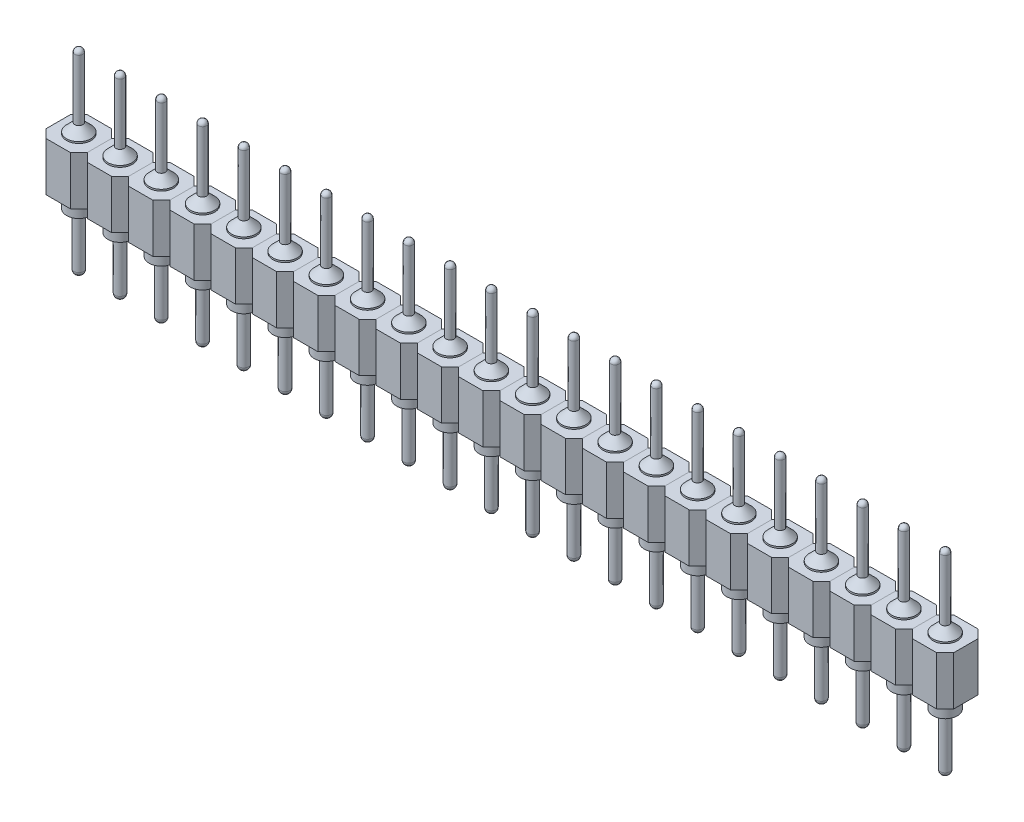
SolidWorks part; units mm, degrees
ref_plane "Спереди" through (0, 0, 0) normal (0, 0, 1) x (1, 0, 0)
ref_plane "Сверху" through (0, 0, 0) normal (0, 1, 0) x (1, 0, 0)
ref_plane "Справа" through (0, 0, 0) normal (1, 0, 0) x (0, 0, -1)
other "Configuration Table"
sketch "Эскиз2" plane through (0, 0, 0) normal (0, 0, 1) x (1, 0, 0)
  line L0 (0, 12.1) -> (0, 0) construction
  line L1 (0, 0) -> (0, 12.1)
  line L2 (0.3, 0.3) -> (0.3, 3.5)
  line L3 (0.3, 3.5) -> (0.75, 3.5)
  line L4 (0.75, 3.5) -> (0.75, 7.6)
  line L5 (0.25, 11.85) -> (0.25, 8.1)
  line L6 (0.25, 8.1) -> (0.75, 7.6)
  circle A0 centre (0, 11.85) radius 0.25
  circle A1 centre (0, 0.3) radius 0.3
  dimension "D1" = 0.5
  dimension "D2" = 0.6
  dimension "D3" = 4
  dimension "D4" = 0.5
  dimension "D5" = 4.1
  dimension "D6" = 3.5
  dimension "D7" = 0.75
revolve "Повернуть1" add sketch "Эскиз2" angle 360 about L1 region at (0.1273, 0.3, 0) region at (0.2877, 5.7983, 0) region at (0.1061, 11.85, 0)
sketch "Эскиз3" plane through (0, 3.5, 0) normal (0, -1, 0) x (1, 0, 0)
  line L0 (0, 1.27) -> (0, -1.27) construction
  line L1 (-0.75, 1.27) -> (0.75, 1.27)
  line L2 (-1.27, 0.75) -> (-1.27, -0.75)
  line L3 (-0.75, -1.27) -> (0.75, -1.27)
  line L4 (1.27, 0.75) -> (1.27, -0.75)
  line L5 (-1.27, 0.75) -> (-0.75, 1.27)
  line L6 (0.75, 1.27) -> (1.27, 0.75)
  line L7 (0.75, -1.27) -> (1.27, -0.75)
  line L8 (-1.27, -0.75) -> (-0.75, -1.27)
  circle A0 centre (0, 0) radius 0.75
  point P0 (-1.27, 1.27)
  point P1 (1.27, -1.27)
  point P2 (-1.27, -1.27)
  point P3 (1.27, 1.27)
  dimension "D2" = 1.5
  dimension "D1" = 2.54
  dimension "D3" = 2.54
extrude "Бобышка-Вытянуть1" add sketch "Эскиз3" against normal blind 3 from offset 1 separate body offset against normal yes
pattern_linear "Линейный массив1" count 22 spacing 2.54 along (-1, 0, 0) of bodies 103 104
